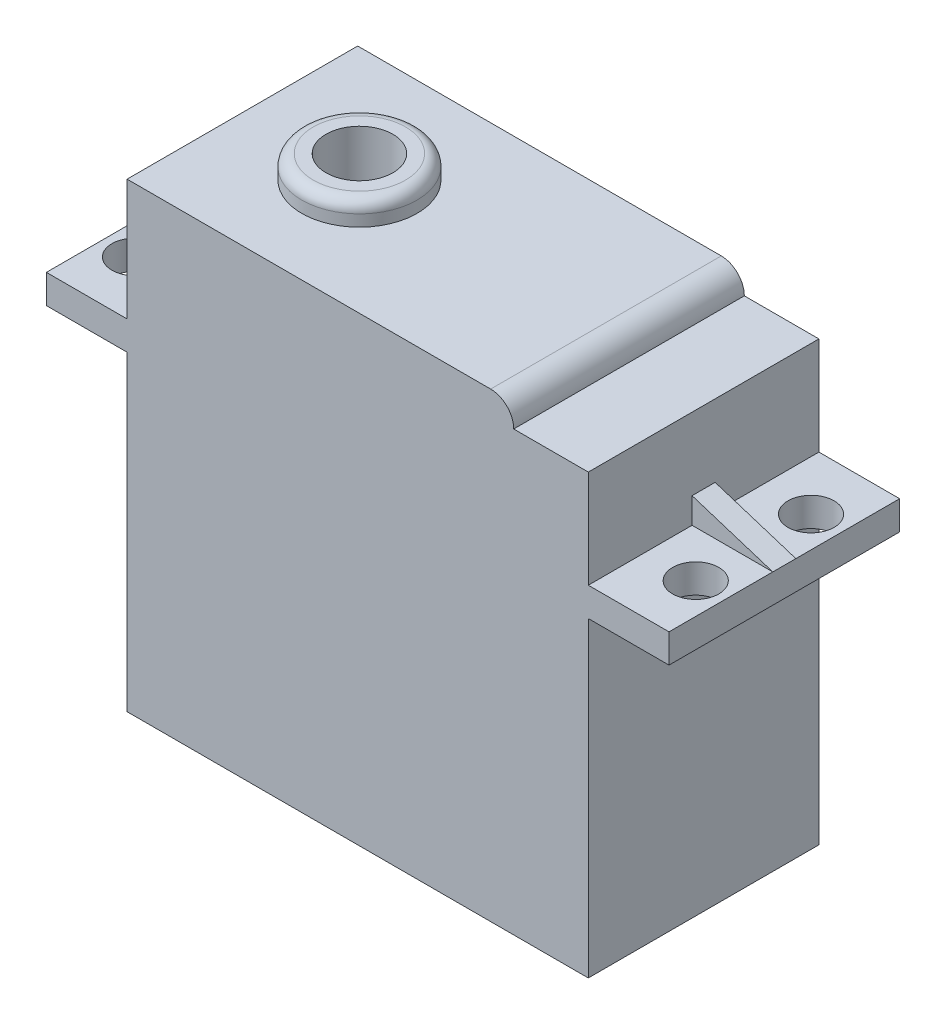
SolidWorks part; units mm, degrees
ref_plane "前视基准面" through (0, 0, 0) normal (0, 0, 1) x (1, 0, 0)
ref_plane "上视基准面" through (0, 0, 0) normal (0, 1, 0) x (1, 0, 0)
ref_plane "右视基准面" through (0, 0, 0) normal (1, 0, 0) x (0, 0, -1)
sketch "草图2" plane through (0, 0, 0) normal (0, 1, 0) x (1, 0, 0)
  line L1 (0, -10) -> (-20, -10)
  line L2 (-20, -10) -> (-20, 10)
  line L3 (-20, 10) -> (20, 10)
  line L4 (20, 10) -> (20, -10)
  line L5 (20, -10) -> (0, -10)
  dimension "D2" = 20
  dimension "D3" = 20
  dimension "D4" = 40
  dimension "D5" = 20
extrude "凸台-拉伸1" add sketch "草图2" against normal blind 27
sketch "草图3" plane through (0, 0, 0) normal (0, 1, 0) x (1, 0, 0)
  line L1 (20, 10) -> (-20, 10) construction
  line L2 (0, 10) -> (27, 10)
  line L3 (27, 10) -> (27, -10)
  line L4 (27, -10) -> (-27, -10)
  line L5 (-27, -10) -> (-27, 10)
  line L6 (-27, 10) -> (0, 10)
  circle A0 centre (-24.315, -5) radius 2
  circle A1 centre (-24.315, 5) radius 2
  circle A2 centre (24.315, -5) radius 2
  circle A3 centre (24.315, 5) radius 2
  dimension "D5" = 4
  dimension "D1" = 27
  dimension "D2" = 20
  dimension "D3" = 54
  dimension "D4" = 20
extrude "凸台-拉伸2" add sketch "草图3" along normal blind 2.5
sketch "草图4" plane through (0, 2.5, 0) normal (0, 1, 0) x (1, 0, 0)
  line L1 (27, 10) -> (-27, 10) construction
  line L2 (0, 10) -> (-20, 10)
  line L3 (-20, 10) -> (-20, -10)
  line L4 (-20, -10) -> (20, -10)
  line L5 (-27, -10) -> (27, -10) construction
  line L6 (20, -10) -> (20, 10)
  line L7 (20, 10) -> (0, 10)
  dimension "D1" = 20
  dimension "D2" = 20
  dimension "D3" = 40
  dimension "D4" = 20
extrude "凸台-拉伸3" add sketch "草图4" along normal blind 8.5
sketch "草图5" plane through (0, 11, 0) normal (0, 1, 0) x (1, 0, 0)
  line L0 (-20, 10) -> (13.5311, 10)
  line L1 (20, 10) -> (-20, 10) construction
  line L2 (-20, 10) -> (-20, -10) construction
  line L3 (13.5311, 10) -> (13.5311, -10)
  line L4 (-20, -10) -> (20, -10) construction
  line L5 (13.5311, -10) -> (-20, -10)
  line L6 (-20, -10) -> (-20, 10)
extrude "凸台-拉伸4" add sketch "草图5" along normal blind 2
fillet "圆角5" radius 2 1 edges at (13.5311, 13, 0)
sketch "草图6" plane through (0, 13, 0) normal (0, 1, 0) x (1, 0, 0)
  line L0 (-27, 0) -> (-9.85, 0)
  line L1 (-27, 10) -> (-27, -10) construction
  circle A0 centre (-9.85, 0) radius 5
  dimension "D2" = 10
  dimension "D1" = 17.15
extrude "凸台-拉伸5" add sketch "草图6" along normal blind 2 contours A0 region at (-9.85, 13, 4.8586)
fillet "圆角7" radius 1 1 edges at (-9.85, 15, 5)
sketch "草图7" plane through (0, 15, 0) normal (0, 1, 0) x (1, 0, 0)
  circle A0 centre (-9.85, 0) radius 2.9
  dimension "D1" = 5.8
extrude "切除-拉伸1" cut sketch "草图7" against normal blind 27
sketch "草图8" plane through (0, 0, 0) normal (0, 0, 1) x (1, 0, 0)
  line L1 (-20, 13) -> (-20, 2.5) construction
  line L4 (-27, 2.5) -> (-20, 2.5) construction
  line L5 (-27, 2.5) -> (-20, 4.7263)
rib "筋8" sketch "草图8" sketch "草图8" thickness 2 extrusion direction parallel to sketch draft on no parameters "D1"=2
mirror "镜向1" about plane through (0, 0, 0) normal (1, 0, 0) of "筋8"
